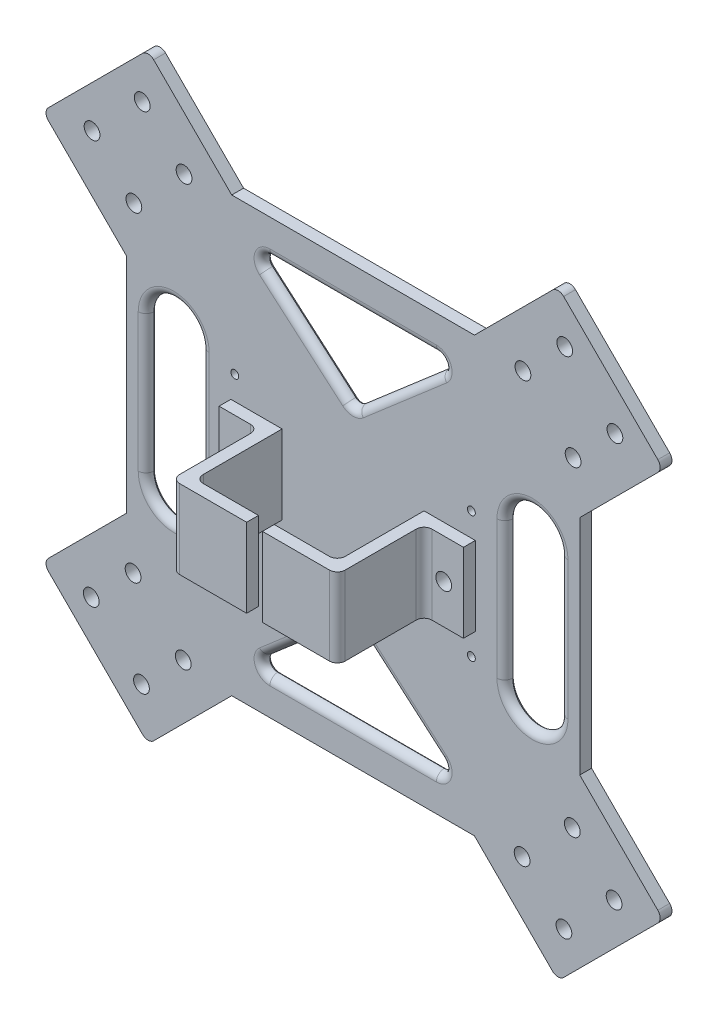
SolidWorks part; units mm, degrees
ref_plane "Front Plane" through (0, 0, 0) normal (0, 0, 1) x (1, 0, 0)
ref_plane "Top Plane" through (0, 0, 0) normal (0, 1, 0) x (1, 0, 0)
ref_plane "Right Plane" through (0, 0, 0) normal (1, 0, 0) x (0, 0, -1)
sketch "Sketch1" plane through (0, 0, 0) normal (0, 0, 1) x (1, 0, 0)
  line L0 (0, 0) -> (0, 47150.9256) construction
  line L1 (0, 0) -> (47150.9256, 0) construction
  line L7 (57.5, -28.28) -> (78.7132, -49.4932)
  line L9 (-30.78, 55) -> (30.78, 55)
  line L10 (-57.5, 28.28) -> (-57.5, -28.28)
  line L11 (-30.78, -55) -> (30.78, -55)
  line L12 (57.5, 28.28) -> (57.5, -28.28)
  line L13 (-57.5, 55) -> (57.5, -55) construction
  line L14 (-57.5, -55) -> (57.5, 55) construction
  line L18 (-30, 16) -> (30, 16) construction
  line L19 (-30, 16) -> (-30, -16) construction
  line L20 (-30, -16) -> (30, -16) construction
  line L21 (30, 16) -> (30, -16) construction
  line L22 (-30, 16) -> (30, -16) construction
  line L23 (-30, -16) -> (30, 16) construction
  line L24 (78.7132, -49.4932) -> (51.9932, -76.2132)
  line L25 (51.9932, -76.2132) -> (30.78, -55)
  line L26 (-57.5, -28.28) -> (-78.7132, -49.4932)
  line L27 (-78.7132, -49.4932) -> (-51.9932, -76.2132)
  line L28 (-51.9932, -76.2132) -> (-30.78, -55)
  line L29 (-51.9932, 76.2132) -> (-30.78, 55)
  line L30 (-78.7132, 49.4932) -> (-51.9932, 76.2132)
  line L31 (-57.5, 28.28) -> (-78.7132, 49.4932)
  line L32 (30.78, 55) -> (51.9932, 76.2132)
  line L33 (51.9932, 76.2132) -> (78.7132, 49.4932)
  line L34 (78.7132, 49.4932) -> (57.5, 28.28)
  line L35 (-28.28, -57.5) -> (-49.4932, -78.7132) [skipped]
  line L36 (-49.4932, -78.7132) -> (-76.2132, -51.9932) [skipped]
  line L37 (-76.2132, -51.9932) -> (-55, -30.78) [skipped]
  line L38 (49.4932, 78.7132) -> (76.2132, 51.9932) [skipped]
  line L39 (76.2132, 51.9932) -> (55, 30.78) [skipped]
  line L40 (28.28, 57.5) -> (49.4932, 78.7132) [skipped]
  circle A4 centre (-30, 16) radius 1
  circle A5 centre (-30, -16) radius 1
  circle A6 centre (30, 16) radius 1
  circle A7 centre (30, -16) radius 1
  arc A8 (-41.3866, 65.6066) -> (41.3866, 65.6066) centre (0, 141.0479) ccw
  arc A9 (-68.1066, 38.8866) -> (-68.1066, -38.8866) centre (-134.0876, 0) cw
  arc A10 (68.1066, 38.8866) -> (68.1066, -38.8866) centre (134.0876, 0) ccw
  arc A11 (-41.3866, -65.6066) -> (41.3866, -65.6066) centre (0, -141.0479) cw
  point P5 (0, 0)
  point P43 (0, 0)
  dimension "D3" = 60
  dimension "D4" = 2
  dimension "D7" = 2
  dimension "D8" = 2
  dimension "D9" = 2
  dimension "D1" = 32
  dimension "D5" = 115
  dimension "D6" = 110
  dimension "D10" = 45
  dimension "D11" = 30
  dimension "D12" = 45
  dimension "D14" = 45
  dimension "D15" = 45
  dimension "D16" = 30
  dimension "D17" = 45
  dimension "D18" = 45
  dimension "D19" = 30
  dimension "D20" = 37.7878
  dimension "D13" = 4
extrude "Boss-Extrude1" add sketch "Sketch1" along normal blind 3 contours L34 L33 L32 L9 L29 L30 L31 L10 L26 L27 L28 L11 L25 L24 L7 L12 A7 A6 A5 A4 region at (0, 0, 0)
sketch "Sketch2" plane through (0, 0, 3) normal (0, 0, 1) x (1, 0, 0)
  line L0 (30.78, 55) -> (57.5, 28.28) construction
  line L1 (44.14, 41.64) -> (71.2882, 68.7882) construction
  line L2 (43.0793, 53.3073) -> (53.6859, 63.9139) construction
  line L3 (43.0793, 53.3073) -> (55.8073, 40.5793) construction
  line L4 (55.8073, 40.5793) -> (66.4139, 51.1859) construction
  line L5 (53.6859, 63.9139) -> (66.4139, 51.1859) construction
  line L6 (43.0793, 53.3073) -> (66.4139, 51.1859) construction
  line L7 (55.8073, 40.5793) -> (53.6859, 63.9139) construction
  line L8 (0, 0) -> (-36037.9104, 34659.328) construction
  line L9 (-57.5, -28.28) -> (-30.78, -55) construction
  line L10 (-78.7132, -49.4932) -> (-51.9932, -76.2132) construction
  line L11 (-65.3532, -62.8532) -> (-37.2147, -34.7147) construction
  line L12 (-78.7132, 49.4932) -> (-51.9932, 76.2132) construction
  line L13 (-57.5, 28.28) -> (-30.78, 55) construction
  line L14 (-66.4139, -51.1859) -> (-55.8073, -40.5793) construction
  line L15 (-66.4139, -51.1859) -> (-53.6859, -63.9139) construction
  line L16 (-53.6859, -63.9139) -> (-43.0793, -53.3073) construction
  line L17 (-55.8073, -40.5793) -> (-43.0793, -53.3073) construction
  line L18 (-66.4139, -51.1859) -> (-43.0793, -53.3073) construction
  line L19 (-53.6859, -63.9139) -> (-55.8073, -40.5793) construction
  line L20 (30.78, -55) -> (57.5, -28.28) construction
  line L21 (-41.3866, 65.6066) -> (-68.1066, 38.8866) construction
  line L22 (-66.207, 51.3928) -> (-53.4791, 64.1207) construction
  line L23 (-66.207, 51.3928) -> (-55.6004, 40.7862) construction
  line L24 (-55.6004, 40.7862) -> (-42.8725, 53.5141) construction
  line L25 (-53.4791, 64.1207) -> (-42.8725, 53.5141) construction
  line L26 (-66.207, 51.3928) -> (-42.8725, 53.5141) construction
  line L27 (-55.6004, 40.7862) -> (-53.4791, 64.1207) construction
  line L28 (-51.9932, 76.2132) -> (-30.78, 55) construction
  line L29 (-57.5, 28.28) -> (-78.7132, 49.4932) construction
  line L30 (-21.1155, 46) -> (21.1155, 46)
  line L31 (42.8725, -53.5141) -> (55.6004, -40.7862) construction
  line L32 (42.8725, -53.5141) -> (53.4791, -64.1207) construction
  line L33 (53.4791, -64.1207) -> (66.207, -51.3928) construction
  line L34 (55.6004, -40.7862) -> (66.207, -51.3928) construction
  line L35 (42.8725, -53.5141) -> (66.207, -51.3928) construction
  line L36 (53.4791, -64.1207) -> (55.6004, -40.7862) construction
  line L37 (22.4225, 42.4861) -> (1.307, 24.256)
  line L38 (-1.307, 24.256) -> (-22.4225, 42.4861)
  line L39 (-30.78, 55) -> (30.78, 55) construction
  line L43 (21.1155, -46) -> (-21.1155, -46)
  line L44 (-22.4225, -42.4861) -> (-1.307, -24.256)
  line L45 (1.307, -24.256) -> (22.4225, -42.4861)
  line L49 (-46, -21.1155) -> (-46, 21.1155) [skipped]
  line L50 (-42.4861, 22.4225) -> (-24.256, 1.307) [skipped]
  line L51 (-24.256, -1.307) -> (-42.4861, -22.4225) [skipped]
  line L52 (24.256, 1.307) -> (42.4861, 22.4225) [skipped]
  line L53 (42.4861, -22.4225) -> (24.256, -1.307) [skipped]
  line L54 (46, 21.1155) -> (46, -21.1155) [skipped]
  line L55 (-45.5, 17.5) -> (-45.5, -17.5) construction
  line L56 (-38.5, 17.5) -> (-38.5, -17.5)
  line L57 (-52.5, 17.5) -> (-52.5, -17.5)
  line L58 (-57.5, 0) -> (-26.4925, 0) construction
  line L59 (-57.5, 28.28) -> (-57.5, -28.28) construction
  line L60 (0, 0) -> (0, 50000) construction
  line L61 (45.5, 17.5) -> (45.5, -17.5) construction
  line L62 (38.5, 17.5) -> (38.5, -17.5)
  line L63 (52.5, 17.5) -> (52.5, -17.5)
  circle A0 centre (43.0793, 53.3073) radius 2
  circle A1 centre (53.6859, 63.9139) radius 2
  circle A2 centre (55.8073, 40.5793) radius 2
  circle A3 centre (66.4139, 51.1859) radius 2
  circle A4 centre (-66.4139, -51.1859) radius 2
  circle A5 centre (-55.8073, -40.5793) radius 2
  circle A6 centre (-43.0793, -53.3073) radius 2
  circle A7 centre (-53.6859, -63.9139) radius 2
  circle A8 centre (-53.4791, 64.1207) radius 2
  circle A9 centre (-42.8725, 53.5141) radius 2
  circle A10 centre (-55.6004, 40.7862) radius 2
  circle A11 centre (-66.207, 51.3928) radius 2
  circle A12 centre (55.6004, -40.7862) radius 2
  circle A13 centre (42.8725, -53.5141) radius 2
  circle A14 centre (66.207, -51.3928) radius 2
  circle A15 centre (53.4791, -64.1207) radius 2
  arc A16 (1.307, 24.256) -> (-1.307, 24.256) centre (0, 25.7698) cw
  arc A17 (21.1155, 46) -> (22.4225, 42.4861) centre (21.1155, 44) cw
  arc A18 (-21.1155, 46) -> (-22.4225, 42.4861) centre (-21.1155, 44) ccw
  circle A19 centre (-30, 16) radius 1 construction
  circle A20 centre (30, 16) radius 1 construction
  arc A24 (-1.307, -24.256) -> (1.307, -24.256) centre (0, -25.7698) cw
  arc A25 (-21.1155, -46) -> (-22.4225, -42.4861) centre (-21.1155, -44) cw
  arc A26 (21.1155, -46) -> (22.4225, -42.4861) centre (21.1155, -44) ccw
  arc A30 (-46, 21.1155) -> (-42.4861, 22.4225) centre (-44, 21.1155) cw [skipped]
  arc A31 (-46, -21.1155) -> (-42.4861, -22.4225) centre (-44, -21.1155) ccw [skipped]
  arc A32 (24.256, -1.307) -> (24.256, 1.307) centre (25.7698, 0) cw [skipped]
  arc A33 (46, 21.1155) -> (42.4861, 22.4225) centre (44, 21.1155) ccw [skipped]
  arc A34 (46, -21.1155) -> (42.4861, -22.4225) centre (44, -21.1155) cw [skipped]
  arc A35 (-24.256, 1.307) -> (-24.256, -1.307) centre (-25.7698, 0) cw [skipped]
  arc A36 (-38.5, 17.5) -> (-52.5, 17.5) centre (-45.5, 17.5) ccw
  arc A37 (-52.5, -17.5) -> (-38.5, -17.5) centre (-45.5, -17.5) ccw
  arc A38 (38.5, 17.5) -> (52.5, 17.5) centre (45.5, 17.5) cw
  arc A39 (52.5, -17.5) -> (38.5, -17.5) centre (45.5, -17.5) cw
  point P4 (54.7466, 52.2466)
  point P18 (-54.7466, -52.2466)
  point P32 (-44.14, -41.64)
  point P38 (-65.3532, 62.8532)
  point P47 (-54.5398, 52.4534)
  point P53 (-52.6697, 53.5593)
  point P63 (54.5398, -52.4534)
  point P79 (0, 23.1276)
  point P82 (26.4925, 46)
  point P85 (-26.4925, 46)
  point P92 (-45.5, 0)
  point P114 (45.5, 0)
  point P120 (0, 0)
  dimension "D8" = 4
  dimension "D9" = 4
  dimension "D10" = 4
  dimension "D11" = 4
  dimension "D12" = 18
  dimension "D19" = 4
  dimension "D20" = 4
  dimension "D21" = 4
  dimension "D22" = 4
  dimension "D29" = 4
  dimension "D30" = 4
  dimension "D31" = 4
  dimension "D32" = 4
  dimension "D40" = 4
  dimension "D41" = 4
  dimension "D42" = 4
  dimension "D43" = 4
  dimension "D47" = 2
  dimension "D50" = 2
  dimension "D53" = 7
  dimension "D1" = 15
  dimension "D2" = 18
  dimension "D3" = 90
  dimension "D4" = 90
  dimension "D5" = 90
  dimension "D6" = 15
  dimension "D7" = 90
  dimension "D13" = 90
  dimension "D14" = 90
  dimension "D15" = 90
  dimension "D16" = 15
  dimension "D17" = 90
  dimension "D18" = 15
  dimension "D23" = 90
  dimension "D24" = 90
  dimension "D25" = 90
  dimension "D26" = 90
  dimension "D27" = 15
  dimension "D28" = 18
  dimension "D33" = 90
  dimension "D34" = 90
  dimension "D35" = 90
  dimension "D36" = 90
  dimension "D37" = 15
  dimension "D38" = 18
  dimension "D39" = 15
  dimension "D44" = 9
  dimension "D45" = 35
  dimension "D46" = 35
  dimension "D48" = 25
  dimension "D49" = 25
  dimension "D52" = 12
  dimension "D54" = 31.0075
  dimension "D55" = 35
  dimension "D51" = 4
extrude "Cut-Extrude1" cut sketch "Sketch2" against normal through all
fillet "Fillet1" radius 2 8 edges at (-51.9932, 76.2132, 1.5) (-78.7132, 49.4932, 1.5) (51.9932, 76.2132, 1.5) (78.7132, 49.4932, 1.5) (78.7132, -49.4932, 1.5) (51.9932, -76.2132, 1.5) (-78.7132, -49.4932, 1.5) (-51.9932, -76.2132, 1.5)
fillet "Fillet2" radius 2 20 edges at (0, 46, 3) (22.99, 44.6972, 3) (11.8647, 33.3711, 3) (0, 23.7698, 3) (-11.8647, 33.3711, 3) (-52.5, 0, 3) (-45.5, 24.5, 3) (-38.5, 0, 3) (11.8647, -33.3711, 3) (22.99, -44.6972, 3) (0, -46, 3) (-22.99, -44.6972, 3) (-11.8647, -33.3711, 3) (38.5, 0, 3) (45.5, 24.5, 3) (52.5, 0, 3) (-22.99, 44.6972, 3) (-45.5, -24.5, 3) (0, -23.7698, 3) (45.5, -24.5, 3)
fillet "Fillet3" radius 2 20 edges at (0, 46, 0) (22.99, 44.6972, 0) (11.8647, 33.3711, 0) (0, 23.7698, 0) (-11.8647, 33.3711, 0) (-52.5, 0, 0) (-45.5, 24.5, 0) (-38.5, 0, 0) (38.5, 0, 0) (45.5, 24.5, 0) (52.5, 0, 0) (11.8647, -33.3711, 0) (22.99, -44.6972, 0) (0, -46, 0) (-22.99, -44.6972, 0) (-11.8647, -33.3711, 0) (-22.99, 44.6972, 0) (-45.5, -24.5, 0) (45.5, -24.5, 0) (0, -23.7698, 0)
sketch3d "3DSketch1" plane through (0, 0, 0) normal (0, 0, 1) x (1, 0, 0)
  dimension "D1" = 55
sketch "Sketch3" plane through (0, 0, 0) normal (0, -1, 0) x (-1, 0, 0)
  line L0 (-21, -8) -> (-21, -26)
  line L1 (30.78, -3) -> (-30.78, -3) construction
  line L5 (-18, -23) -> (-18, -3)
  line L7 (0, 0) -> (0, -50000) construction
  line L8 (0, 0) -> (-50000, 0) construction
  line L15 (-31, -3) -> (-31, -6)
  line L16 (-31, -6) -> (-23, -6)
  line L18 (-31, -3) -> (-18, -3)
  line L23 (-19, -28) -> (-2, -28)
  line L24 (-2, -28) -> (-2, -25)
  line L25 (-2, -25) -> (-16, -25)
  line L26 (2, -28) -> (2, -25)
  line L27 (2, -25) -> (16, -25)
  line L28 (19, -28) -> (2, -28)
  line L29 (18, -23) -> (18, -3)
  line L30 (21, -8) -> (21, -26)
  line L31 (31, -6) -> (23, -6)
  line L32 (31, -3) -> (18, -3)
  line L33 (31, -3) -> (31, -6)
  arc A0 (21, -8) -> (23, -6) centre (23, -8) cw
  arc A1 (-23, -6) -> (-21, -8) centre (-23, -8) cw
  arc A2 (19, -28) -> (21, -26) centre (19, -26) ccw
  arc A3 (16, -25) -> (18, -23) centre (16, -23) ccw
  arc A4 (-21, -26) -> (-19, -28) centre (-19, -26) ccw
  arc A5 (-18, -23) -> (-16, -25) centre (-16, -23) ccw
  point P11 (0, -3)
  point P25 (21, -6)
  point P28 (-21, -6)
  point P33 (21, -28)
  point P37 (18, -25)
  point P42 (-21, -28)
  point P45 (-18, -25)
  dimension "D6" = 2
  dimension "D2" = 2
  dimension "D1" = 18
  dimension "D3" = 3
  dimension "D4" = 3
  dimension "D5" = 25
  dimension "D7" = 3
  dimension "D8" = 10
extrude "Boss-Extrude2" add sketch "Sketch3" along normal mid plane 20
sketch "Sketch4" plane through (0, 0, 6) normal (0, 0, 1) x (1, 0, 0)
  line L0 (0, 0) -> (0, -50000) construction
  line L1 (31, -10) -> (31, 10) construction
  line L2 (31, 10) -> (23, 10) construction
  circle A0 centre (26, 0) radius 2
  circle A1 centre (-26, 0) radius 2
  dimension "D1" = 4
  dimension "D3" = 10
  dimension "D2" = 5
extrude "Cut-Extrude2" cut sketch "Sketch4" against normal through all
